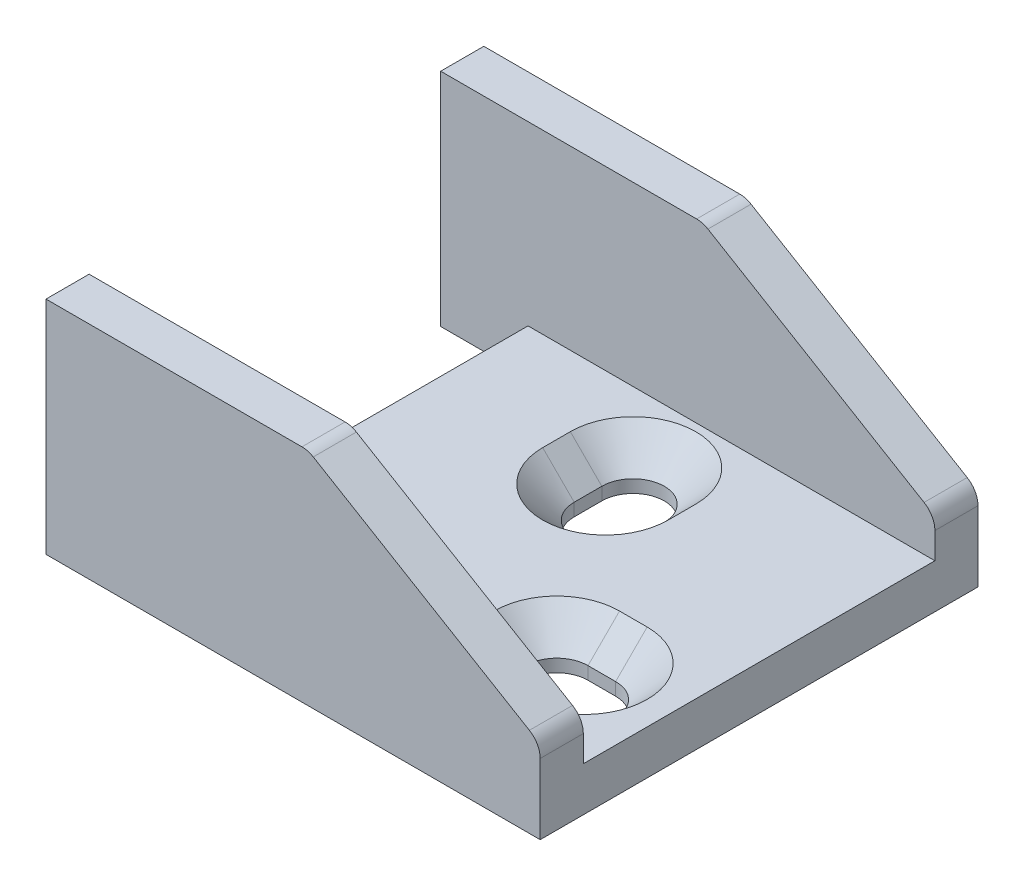
SolidWorks part; units mm, degrees
ref_plane "Front Plane" through (0, 0, 0) normal (0, 0, 1) x (1, 0, 0)
ref_plane "Top Plane" through (0, 0, 0) normal (0, 1, 0) x (1, 0, 0)
ref_plane "Right Plane" through (0, 0, 0) normal (1, 0, 0) x (0, 0, -1)
sketch "Sketch1" plane through (0, 0, 0) normal (0, 1, 0) x (1, 0, 0)
  line L1 (0, 0) -> (36.8, 0)
  line L2 (0, 0) -> (0, 39.6)
  line L3 (0, 39.6) -> (36.8, 39.6)
  line L4 (36.8, 0) -> (36.8, 39.6)
  dimension "D1" = 36.8
  dimension "D2" = 39.6
extrude "Boss-Extrude1" add sketch "Sketch1" along normal blind 4
sketch "Sketch2" plane through (0, 0, 0) normal (0, 1, 0) x (1, 0, 0)
  line L0 (36.8, 19.8) -> (0, 19.8) construction
  line L1 (36.8, 39.6) -> (-7.9, 39.6)
  line L2 (36.8, 39.6) -> (36.8, 35.7)
  line L3 (36.8, 35.7) -> (-7.9, 35.7)
  line L4 (-7.9, 39.6) -> (-7.9, 35.7)
  line L5 (36.8, 0) -> (36.8, 39.6) construction
  line L6 (0, 39.6) -> (0, 0) construction
  line L7 (36.8, 0) -> (36.8, 3.9)
  line L8 (-7.9, 0) -> (-7.9, 3.9)
  line L9 (36.8, 0) -> (-7.9, 0)
  line L10 (36.8, 3.9) -> (-7.9, 3.9)
  dimension "D1" = 3.9
  dimension "D2" = 44.7
extrude "Boss-Extrude2" add sketch "Sketch2" along normal blind 20
sketch "Sketch3" plane through (0, 4, 0) normal (0, 1, 0) x (1, 0, 0)
  line L0 (26.475, 11.825) -> (28.975, 11.825) construction
  line L1 (26.475, 14.65) -> (28.975, 14.65)
  line L2 (26.475, 9) -> (28.975, 9)
  line L3 (15.875, 29.325) -> (15.875, 26.825) construction
  line L4 (18.7, 29.325) -> (18.7, 26.825)
  line L5 (13.05, 29.325) -> (13.05, 26.825)
  line L6 (-7.9, 0) -> (36.8, 0) construction
  line L7 (36.8, 3.9) -> (36.8, 35.7) construction
  arc A0 (26.475, 14.65) -> (26.475, 9) centre (26.475, 11.825) ccw
  arc A1 (28.975, 9) -> (28.975, 14.65) centre (28.975, 11.825) ccw
  arc A2 (18.7, 29.325) -> (13.05, 29.325) centre (15.875, 29.325) ccw
  arc A3 (13.05, 26.825) -> (18.7, 26.825) centre (15.875, 26.825) ccw
  point P2 (27.725, 11.825)
  point P9 (15.875, 28.075)
  point P14 (27.725, 9)
  dimension "D3" = 8.15
  dimension "D4" = 8.15
  dimension "D1" = 5.65
  dimension "D2" = 5.65
  dimension "D5" = 9
  dimension "D6" = 5
  dimension "D7" = 18.1
  dimension "D8" = 24
extrude "Cut-Extrude1" cut sketch "Sketch3" against normal up to next
chamfer "Chamfer1" distance 2.85 angle 45 8 edges at (23.65, 4, -11.825) (27.725, 4, -9) (31.8, 4, -11.825) (27.725, 4, -14.65) (13.05, 4, -28.075) (15.875, 4, -24) (18.7, 4, -28.075) (15.875, 4, -32.15)
sketch "Sketch4" plane through (0, 0, -39.6) normal (0, 0, -1) x (-1, 0, 0)
  line L0 (-36.8, 20) -> (-36.8, 7.5)
  line L1 (-36.8, 20) -> (-36.8, 0) construction
  line L2 (-36.8, 7.5) -> (-15.8, 20)
  line L3 (-36.8, 20) -> (7.9, 20) construction
  line L4 (-15.8, 20) -> (-36.8, 20)
  dimension "D1" = 7.5
  dimension "D2" = 21
extrude "Cut-Extrude2" cut sketch "Sketch4" against normal through all
fillet "Fillet1" radius 2 4 edges at (36.8, 7.5, -1.95) (36.8, 7.5, -37.65) (15.8, 20, -37.65) (15.8, 20, -1.95)
